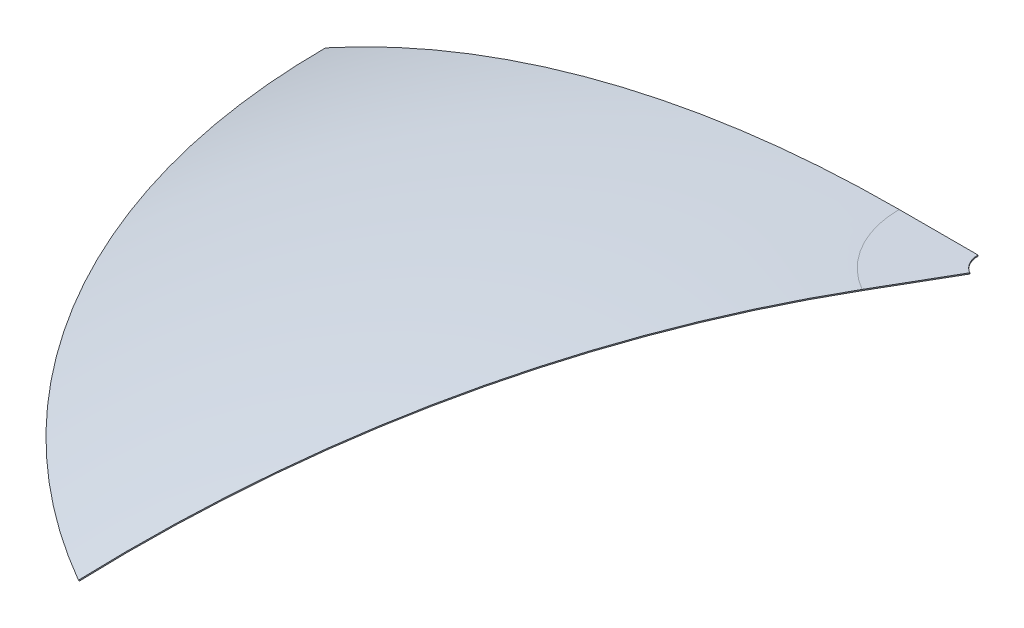
SolidWorks part; units mm, degrees
ref_plane "Front Plane" through (0, 0, 0) normal (0, 0, 1) x (1, 0, 0)
ref_plane "Top Plane" through (0, 0, 0) normal (0, 1, 0) x (1, 0, 0)
ref_plane "Right Plane" through (0, 0, 0) normal (1, 0, 0) x (0, 0, -1)
sketch "Sketch1" plane through (0, 0, 0) normal (0, 0, 1) x (1, 0, 0)
  line L0 (45, 1.5) -> (-45, 1.5) construction
  line L1 (45, 1.5) -> (-45, 1.5) construction
  line L2 (10, 1.5) -> (-10, 1.5) construction
  line L3 (10, 1.5) -> (-10, 1.5) construction
  line L4 (-45, 1.5) -> (-10, 1.5)
  line L6 (-45, 2) -> (-10, 2)
  line L7 (-10, 2) -> (-10, 1.5)
  line L8 (-299.7402, -63.211) -> (-299.5, -63.6495)
  line L9 (0, -998.5) -> (0, 49001.5) construction
  arc A1 (-46.0019, 1.4991) -> (-299.5, -63.6495) centre (-45, -528.1639) ccw
  arc A2 (-45, 1.5) -> (-46.0019, 1.4991) centre (-45, -528.1639) ccw
  arc A3 (-46.0028, 1.9991) -> (-299.7402, -63.211) centre (-45, -528.1639) ccw
  arc A4 (-45, 2) -> (-46.0028, 1.9991) centre (-45, -528.1639) ccw
  point P9 (0, 0)
  point P17 (0, 1.5)
  point P18 (0, 0)
  point P19 (0, 0)
  dimension "D1" = 0.5
  dimension "D2" = 1.0019
  dimension "D3" = 264.4748
  dimension "D4" = 1.0019
  dimension "D5" = 35
revolve "Revolve1" add sketch "Sketch1" angle 60 about L9
sketch "Sketch3" plane through (0, 2, 0) normal (0, 1, 0) x (1, 0, 0)
  line L0 (-10, 0) -> (-5, -8.6603)
  arc A0 (-10, 0) -> (-5, -8.6603) centre (0, 0) ccw construction
  arc A1 (-10, 0) -> (-5, -8.6603) centre (0, 0) ccw
extrude "Boss-Extrude1" [suppressed] add sketch "Sketch3" against normal up to surface (0.5 mm away) up to face at (-22.2203, 1.5, 12.8289)
